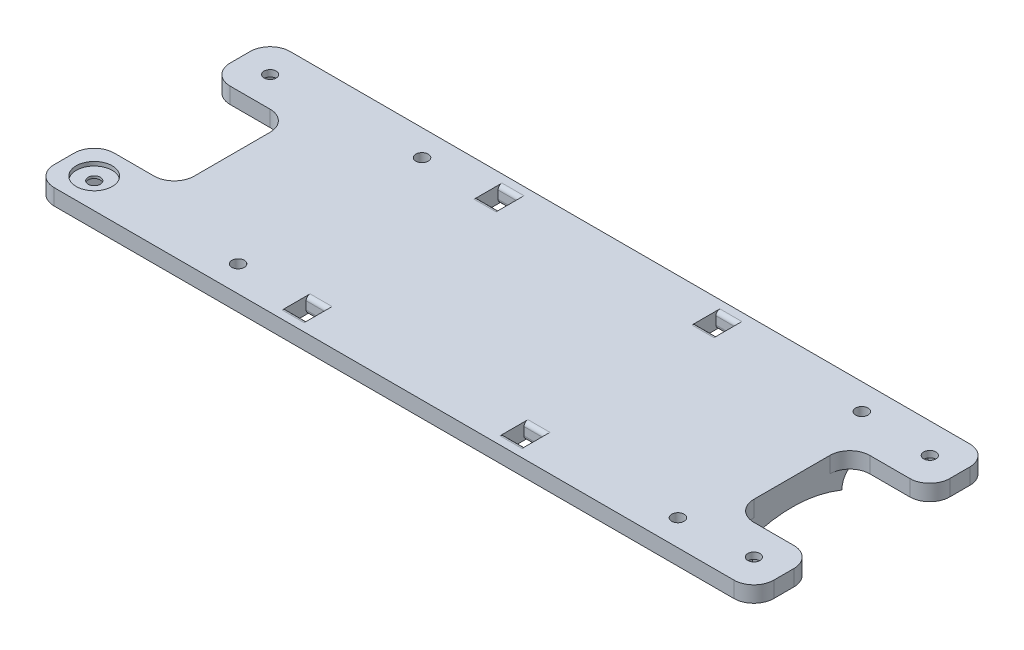
SolidWorks part; units mm, degrees
ref_plane "Front Plane" through (0, 0, 0) normal (0, 0, 1) x (1, 0, 0)
ref_plane "Top Plane" through (0, 0, 0) normal (0, 1, 0) x (1, 0, 0)
ref_plane "Right Plane" through (0, 0, 0) normal (1, 0, 0) x (0, 0, -1)
sketch "Sketch1" plane through (0, 0, 0) normal (0, 1, 0) x (1, 0, 0)
  line L0 (-94.307, 45.1379) -> (-94.307, 16.1379)
  line L1 (-68.307, 1.1379) -> (45.693, 1.1379)
  line L2 (45.693, 16.1379) -> (45.693, 45.1379)
  line L3 (45.693, 60.1379) -> (-68.307, 60.1379)
  line L4 (-68.307, 60.1379) -> (-114.307, 60.1379)
  line L5 (-114.307, 60.1379) -> (-114.307, 45.1379)
  line L6 (-114.307, 45.1379) -> (-94.307, 45.1379)
  line L7 (-68.307, 1.1379) -> (-114.307, 1.1379)
  line L8 (-114.307, 1.1379) -> (-114.307, 16.1379)
  line L9 (-114.307, 16.1379) -> (-94.307, 16.1379)
  line L10 (45.693, 1.1379) -> (65.693, 1.1379)
  line L11 (65.693, 1.1379) -> (65.693, 16.1379)
  line L12 (65.693, 16.1379) -> (45.693, 16.1379)
  line L13 (45.693, 60.1379) -> (65.693, 60.1379)
  line L14 (65.693, 60.1379) -> (65.693, 45.1379)
  line L15 (65.693, 45.1379) -> (45.693, 45.1379)
  dimension "D1" = 59
  dimension "D2" = 140
  dimension "D3" = 20
  dimension "D4" = 15
  dimension "D5" = 15
  dimension "D6" = 20
  dimension "D7" = 15
  dimension "D8" = 15
  dimension "D10" = 20
  dimension "D11" = 20
extrude "Boss-Extrude1" add sketch "Sketch1" along normal blind 4
sketch "Sketch2" plane through (0, 4, 0) normal (0, 1, 0) x (1, 0, 0)
  line L0 (-91.307, 56.1379) -> (-91.307, 5.1379)
  line L1 (-91.307, 5.1379) -> (42.693, 5.1379)
  line L2 (42.693, 5.1379) -> (42.693, 56.1379)
  line L3 (42.693, 56.1379) -> (-91.307, 56.1379)
  line L4 (-94.307, 45.1379) -> (-94.307, 16.1379) construction
  line L5 (-114.307, 1.1379) -> (65.693, 1.1379) construction
  line L6 (65.693, 60.1379) -> (-114.307, 60.1379) construction
  line L7 (45.693, 16.1379) -> (45.693, 45.1379) construction
  circle A0 centre (40.193, 53.6379) radius 1.55
  circle A1 centre (-69.807, 53.6379) radius 1.55
  circle A2 centre (-69.807, 7.6379) radius 1.55
  circle A3 centre (40.193, 7.6379) radius 1.55
  dimension "D8" = 134
  dimension "D1" = 3
  dimension "D2" = 4
  dimension "D3" = 51
  dimension "D4" = 46
  dimension "D5" = 2.5
  dimension "D6" = 110
  dimension "D7" = 2.5
  dimension "D9" = 4
  dimension "D10" = 3
  dimension "D11" = 2.5
extrude "Cut-Extrude3" cut sketch "Sketch2" against normal through all contours A1 | A0 | A3 | A2
sketch "Sketch4" plane through (-31.1286, 4, 0) normal (0, -1, 0) x (-1, 0, 0)
  line L0 (-2.0878, 37.6677) -> (-4.2934, 41.8667)
  line L1 (-4.2934, 22.1365) -> (-2.0878, 26.3345)
  line L2 (-6.4961, 26.3345) -> (-4.2934, 22.1365)
  line L3 (-4.2934, 41.8667) -> (-6.4961, 37.6677)
  line L4 (-7.5369, 37.6677) -> (-9.7405, 41.8667)
  line L5 (-9.7405, 22.1365) -> (-7.5369, 26.3345)
  line L6 (-11.9452, 26.3345) -> (-9.7405, 22.1365)
  line L7 (-9.7405, 41.8667) -> (-11.9452, 37.6677)
  line L8 (-12.985, 37.6677) -> (-15.1887, 41.8667)
  line L9 (-15.1887, 22.1365) -> (-12.985, 26.3345)
  line L10 (-17.3923, 26.3345) -> (-15.1887, 22.1365)
  line L11 (-15.1887, 41.8667) -> (-17.3923, 37.6677)
  line L12 (11.3891, 26.0259) -> (11.3891, 23.4065)
  line L13 (5.0401, 28.613) -> (7.2864, 28.613)
  line L14 (0.9374, 23.4065) -> (0.9374, 26.0259)
  line L15 (11.1698, 23.1873) -> (1.1566, 23.1873)
  line L16 (2.1597, 24.8492) -> (10.1677, 24.8492)
  line L17 (2.1597, 25.7729) -> (2.1597, 24.8492)
  line L18 (7.4015, 26.9283) -> (4.925, 26.9283)
  line L19 (10.1677, 24.8492) -> (10.1677, 25.7729)
  line L20 (3.775, 40.7584) -> (11.1698, 40.7584)
  line L21 (11.1698, 35.353) -> (3.775, 35.353)
  line L22 (11.3891, 36.7956) -> (11.3891, 35.5722)
  line L23 (3.777, 37.0159) -> (11.1698, 37.0159)
  line L24 (11.1698, 39.0955) -> (3.777, 39.0955)
  line L25 (11.3891, 40.5391) -> (11.3891, 39.3148)
  line L26 (10.0685, 32.8546) -> (1.1566, 32.8546)
  line L27 (10.0685, 34.4273) -> (10.0685, 32.8546)
  line L28 (11.1698, 34.647) -> (10.2877, 34.647)
  line L29 (11.3891, 29.505) -> (11.3891, 34.4273)
  line L30 (10.2877, 29.2848) -> (11.1698, 29.2848)
  line L31 (10.0685, 31.0771) -> (10.0685, 29.505)
  line L32 (1.1566, 31.0771) -> (10.0685, 31.0771)
  line L33 (0.9374, 32.6364) -> (0.9374, 31.2964)
  spline S0 degree 3 poles (-2.0878, 26.3345) (-4.2032, 31.7727) (-4.2032, 32.2315) (-2.0878, 37.6677) knots 4 4 4 4 5 5 5 5
  spline S1 degree 3 poles (-6.4961, 37.6677) (-4.3817, 32.2315) (-4.3817, 31.7727) (-6.4961, 26.3345) knots 1 1 1 1 2 2 2 2
  spline S2 degree 3 poles (-7.5369, 26.3345) (-9.6513, 31.7727) (-9.6513, 32.2315) (-7.5369, 37.6677) knots 4 4 4 4 5 5 5 5
  spline S3 degree 3 poles (-11.9452, 37.6677) (-9.8298, 32.2315) (-9.8298, 31.7727) (-11.9452, 26.3345) knots 1 1 1 1 2 2 2 2
  spline S4 degree 3 poles (-12.985, 26.3345) (-15.1003, 31.7727) (-15.1003, 32.2315) (-12.985, 37.6677) knots 4 4 4 4 5 5 5 5
  spline S5 degree 3 poles (-17.3923, 37.6677) (-15.2779, 32.2315) (-15.2779, 31.7727) (-17.3923, 26.3345) knots 1 1 1 1 2 2 2 2
  spline S6 degree 3 poles (10.6707, 28.0401) (11.1579, 27.664) (11.3891, 27.0434) (11.3891, 26.0259) knots 10 10 10 10 11 11 11 11
  spline S7 degree 3 poles (7.2864, 28.613) (8.9324, 28.613) (10.006, 28.5952) (10.6707, 28.0401) knots 9 9 9 9 10 10 10 10
  spline S8 degree 3 poles (1.6557, 28.0401) (2.3205, 28.5952) (3.394, 28.613) (5.0401, 28.613) knots 7 7 7 7 8 8 8 8
  spline S9 degree 3 poles (0.9374, 26.0259) (0.9374, 27.0434) (1.1686, 27.664) (1.6557, 28.0401) knots 6 6 6 6 7 7 7 7
  spline S10 degree 3 poles (0.9959, 23.2448) (0.9612, 23.28) (0.9374, 23.3282) (0.9374, 23.4065) knots 4 4 4 4 5 5 5 5
  spline S11 degree 3 poles (1.1566, 23.1873) (1.0783, 23.1873) (1.0306, 23.2101) (0.9959, 23.2448) knots 3 3 3 3 4 4 4 4
  spline S12 degree 3 poles (11.3315, 23.2448) (11.2958, 23.2101) (11.2492, 23.1873) (11.1698, 23.1873) knots 1 1 1 1 2 2 2 2
  spline S13 degree 3 poles (11.3891, 23.4065) (11.3891, 23.3282) (11.3653, 23.28) (11.3315, 23.2448) knots 0 0 0 0 1 1 1 1
  spline S14 degree 3 poles (2.4515, 26.6128) (2.2252, 26.4243) (2.1597, 26.1807) (2.1597, 25.7729) knots 5 5 5 5 6 6 6 6
  spline S15 degree 3 poles (4.925, 26.9283) (3.5052, 26.9283) (2.8007, 26.9035) (2.4515, 26.6128) knots 4 4 4 4 5 5 5 5
  spline S16 degree 3 poles (9.875, 26.6128) (9.5257, 26.9035) (8.8213, 26.9283) (7.4015, 26.9283) knots 2 2 2 2 3 3 3 3
  spline S17 degree 3 poles (10.1677, 25.7729) (10.1677, 26.1807) (10.1012, 26.4243) (9.875, 26.6128) knots 1 1 1 1 2 2 2 2
  spline S18 degree 3 poles (1.5545, 40.1606) (2.1111, 40.6398) (2.7759, 40.7584) (3.775, 40.7584) knots 20 20 20 20 21 21 21 21
  spline S19 degree 3 poles (0.8054, 38.0607) (0.8054, 39.09) (1.0812, 39.7528) (1.5545, 40.1606) knots 19 19 19 19 20 20 20 20
  spline S20 degree 3 poles (1.5535, 35.927) (1.0644, 36.371) (0.8054, 37.0432) (0.8054, 38.0607) knots 18 18 18 18 19 19 19 19
  spline S21 degree 3 poles (3.775, 35.353) (2.6985, 35.353) (2.0238, 35.4993) (1.5535, 35.927) knots 17 17 17 17 18 18 18 18
  spline S22 degree 3 poles (11.3315, 35.4115) (11.2958, 35.3758) (11.2492, 35.353) (11.1698, 35.353) knots 15 15 15 15 16 16 16 16
  spline S23 degree 3 poles (11.3891, 35.5722) (11.3891, 35.4934) (11.3653, 35.4452) (11.3315, 35.4115) knots 14 14 14 14 15 15 15 15
  spline S24 degree 3 poles (11.3315, 36.9563) (11.3653, 36.9226) (11.3891, 36.8745) (11.3891, 36.7956) knots 12 12 12 12 13 13 13 13
  spline S25 degree 3 poles (11.1698, 37.0159) (11.2492, 37.0159) (11.2958, 36.9916) (11.3315, 36.9563) knots 11 11 11 11 12 12 12 12
  spline S26 degree 3 poles (2.2738, 37.3249) (2.5348, 37.0878) (2.9783, 37.0159) (3.777, 37.0159) knots 9 9 9 9 10 10 10 10
  spline S27 degree 3 poles (1.9941, 38.0393) (1.9941, 37.7327) (2.0794, 37.5016) (2.2738, 37.3249) knots 8 8 8 8 9 9 9 9
  spline S28 degree 3 poles (2.2719, 38.7869) (2.0853, 38.6168) (1.9941, 38.3757) (1.9941, 38.0393) knots 7 7 7 7 8 8 8 8
  spline S29 degree 3 poles (3.777, 39.0955) (3.0061, 39.0955) (2.5477, 39.037) (2.2719, 38.7869) knots 6 6 6 6 7 7 7 7
  spline S30 degree 3 poles (11.3315, 39.154) (11.2958, 39.1188) (11.2492, 39.0955) (11.1698, 39.0955) knots 4 4 4 4 5 5 5 5
  spline S31 degree 3 poles (11.3891, 39.3148) (11.3891, 39.2364) (11.3653, 39.1888) (11.3315, 39.154) knots 3 3 3 3 4 4 4 4
  spline S32 degree 3 poles (11.3315, 40.6999) (11.3653, 40.6656) (11.3891, 40.617) (11.3891, 40.5391) knots 1 1 1 1 2 2 2 2
  spline S33 degree 3 poles (11.1698, 40.7584) (11.2492, 40.7584) (11.2958, 40.7346) (11.3315, 40.6999) knots 0 0 0 0 1 1 1 1
  spline S34 degree 3 poles (10.126, 34.5895) (10.0913, 34.5543) (10.0685, 34.5061) (10.0685, 34.4273) knots 17 17 17 17 18 18 18 18
  spline S35 degree 3 poles (10.2877, 34.647) (10.2094, 34.647) (10.1607, 34.6227) (10.126, 34.5895) knots 16 16 16 16 17 17 17 17
  spline S36 degree 3 poles (11.3315, 34.5895) (11.2958, 34.6227) (11.2492, 34.647) (11.1698, 34.647) knots 14 14 14 14 15 15 15 15
  spline S37 degree 3 poles (11.3891, 34.4273) (11.3891, 34.5061) (11.3653, 34.5543) (11.3315, 34.5895) knots 13 13 13 13 14 14 14 14
  spline S38 degree 3 poles (11.3315, 29.3433) (11.3653, 29.379) (11.3891, 29.4261) (11.3891, 29.505) knots 11 11 11 11 12 12 12 12
  spline S39 degree 3 poles (11.1698, 29.2848) (11.2492, 29.2848) (11.2958, 29.3086) (11.3315, 29.3433) knots 10 10 10 10 11 11 11 11
  spline S40 degree 3 poles (10.126, 29.3433) (10.1607, 29.3086) (10.2094, 29.2848) (10.2877, 29.2848) knots 8 8 8 8 9 9 9 9
  spline S41 degree 3 poles (10.0685, 29.505) (10.0685, 29.4261) (10.0913, 29.379) (10.126, 29.3433) knots 7 7 7 7 8 8 8 8
  spline S42 degree 3 poles (0.9959, 31.1357) (1.0306, 31.1) (1.0783, 31.0771) (1.1566, 31.0771) knots 4 4 4 4 5 5 5 5
  spline S43 degree 3 poles (0.9374, 31.2964) (0.9374, 31.2185) (0.9612, 31.1699) (0.9959, 31.1357) knots 3 3 3 3 4 4 4 4
  spline S44 degree 3 poles (0.9959, 32.7971) (0.9612, 32.7619) (0.9374, 32.7142) (0.9374, 32.6364) knots 1 1 1 1 2 2 2 2
  spline S45 degree 3 poles (1.1566, 32.8546) (1.0783, 32.8546) (1.0306, 32.8318) (0.9959, 32.7971) knots 0 0 0 0 1 1 1 1
extrude "Boss-Extrude2" [suppressed] add sketch "Sketch4" against normal blind 1.6
fillet "Fillet1" radius 5 12 edges at (-114.307, 2, -45.1379) (-114.307, 2, -60.1379) (-114.307, 2, -1.1379) (65.693, 2, -60.1379) (45.693, 2, -45.1379) (65.693, 2, -45.1379) (65.693, 2, -1.1379) (-114.307, 2, -16.1379) (65.693, 2, -16.1379) (45.693, 2, -16.1379) (-94.307, 2, -16.1379) (-94.307, 2, -45.1379)
sketch "Sketch5" plane through (0, 4, 0) normal (0, 1, 0) x (1, 0, 0)
  line L0 (60.693, 60.1379) -> (-109.307, 60.1379) construction
  line L1 (-114.307, 55.1379) -> (-114.307, 50.1379) construction
  line L2 (-99.307, 16.1379) -> (-109.307, 16.1379) construction
  line L3 (-114.307, 11.1379) -> (-114.307, 6.1379) construction
  line L4 (60.693, 16.1379) -> (50.693, 16.1379) construction
  line L5 (65.693, 6.1379) -> (65.693, 11.1379) construction
  line L6 (65.693, 50.1379) -> (65.693, 55.1379) construction
  circle A0 centre (-106.807, 52.6379) radius 1.525
  circle A2 centre (-106.807, 8.6379) radius 1.525
  circle A3 centre (58.193, 8.6379) radius 1.525
  circle A4 centre (58.193, 52.6379) radius 1.525
  circle A5 centre (-106.807, 8.6379) radius 4.5
  dimension "D1" = 3.05
  dimension "D7" = 3.05
  dimension "D10" = 3.05
  dimension "D13" = 3.05
  dimension "D14" = 9
  dimension "D2" = 7.5
  dimension "D3" = 7.5
  dimension "D5" = 7.5
  dimension "D6" = 7.5
  dimension "D8" = 7.5
  dimension "D9" = 7.5
  dimension "D11" = 7.5
  dimension "D12" = 7.5
extrude "Cut-Extrude4" cut sketch "Sketch5" against normal blind 10 contours A0 | A2 | A3 | A4
extrude "Cut-Extrude5" cut sketch "Sketch5<3>" against normal blind 1 contours A5
sketch "Sketch5<3>" plane through (0, 4, 0) normal (0, 1, 0) x (1, 0, 0) same geometry as "Sketch5"
sketch "Sketch6" plane through (0, 0, 0) normal (0, -1, 0) x (1, 0, 0)
  line L1 (-104.663, -11.0193) -> (-103.6727, -7.9718)
  line L2 (-103.6727, -7.9718) -> (-105.8167, -5.5905)
  line L3 (-105.8167, -5.5905) -> (-108.951, -6.2566)
  line L4 (-108.951, -6.2566) -> (-109.9413, -9.304)
  line L5 (-109.9413, -9.304) -> (-107.7973, -11.6854)
  line L6 (-107.7973, -11.6854) -> (-104.663, -11.0193)
  line L7 (58.7701, -11.7898) -> (61.2112, -9.7141)
  line L8 (61.2112, -9.7141) -> (60.6341, -6.5622)
  line L9 (60.6341, -6.5622) -> (57.6159, -5.486)
  line L10 (57.6159, -5.486) -> (55.1748, -7.5618)
  line L11 (55.1748, -7.5618) -> (55.7519, -10.7137)
  line L12 (55.7519, -10.7137) -> (58.7701, -11.7898)
  line L13 (60.6824, -50.6205) -> (57.6905, -49.4733)
  line L14 (57.6905, -49.4733) -> (55.2011, -51.4908)
  line L15 (55.2011, -51.4908) -> (55.7035, -54.6554)
  line L16 (55.7035, -54.6554) -> (58.6955, -55.8026)
  line L17 (58.6955, -55.8026) -> (61.1849, -53.7851)
  line L18 (61.1849, -53.7851) -> (60.6824, -50.6205)
  line L19 (-103.607, -52.4732) -> (-105.3497, -49.7842)
  line L20 (-105.3497, -49.7842) -> (-108.5497, -49.949)
  line L21 (-108.5497, -49.949) -> (-110.0071, -52.8027)
  line L22 (-110.0071, -52.8027) -> (-108.2644, -55.4916)
  line L23 (-108.2644, -55.4916) -> (-105.0643, -55.3269)
  line L24 (-105.0643, -55.3269) -> (-103.607, -52.4732)
  circle A0 centre (-106.807, -8.6379) radius 2.775 construction
  circle A1 centre (58.193, -8.6379) radius 2.775 construction
  circle A2 centre (58.193, -52.6379) radius 2.775 construction
  circle A3 centre (-106.807, -52.6379) radius 2.775 construction
  circle A4 centre (58.193, -52.6379) radius 1.525 construction
  point P40 (-104.3356, -53.9)
  dimension "D1" = 5.55
  dimension "D2" = 5.55
  dimension "D3" = 5.55
  dimension "D4" = 5.55
extrude "Cut-Extrude6" cut sketch "Sketch6" against normal blind 2.4
sketch "Sketch8" plane through (0, 0, 0) normal (0, -1, 0) x (1, 0, 0)
  line L0 (45.693, -18.1379) -> (-94.307, -18.1379)
  line L3 (-94.307, -18.1379) -> (-94.307, -43.1379)
  line L4 (-94.307, -43.1379) -> (45.693, -43.1379)
  line L5 (45.693, -43.1379) -> (45.693, -18.1379)
  line L6 (-94.307, -40.1379) -> (-94.307, -21.1379) construction
  line L7 (45.693, -21.1379) -> (45.693, -40.1379) construction
  line L8 (-94.307, -30.6379) -> (45.693, -30.6379) construction
  dimension "D1" = 25
  dimension "D2" = 12.5
extrude "Boss-Extrude4" add sketch "Sketch8" along normal blind 5
sketch "Sketch9" plane through (-94.307, 0, -95.4449) normal (1, 0, 0) x (0, 0, -1)
  line L0 (-52.307, -5) -> (-77.307, -5)
  line L1 (-77.307, -5) -> (-52.307, -5) construction
  spline S0 degree 2 poles (-52.307, -5) (-64.7313, 0.0282) (-77.307, -5) knots 0 0 0 1 1 1
  point P8 (0, 0)
  point P12 (0, 0)
  point P14 (0, 0)
  dimension "D1" = 2.5
extrude "Cut-Extrude7" cut sketch "Sketch9" along normal through all
sketch "Sketch12" plane through (0, 0, 0) normal (0, -1, 0) x (1, 0, 0)
  line L0 (-54.307, -9.1379) -> (-48.807, -9.1379)
  line L1 (-48.807, -9.1379) -> (-48.807, -4.1379)
  line L2 (-48.807, -4.1379) -> (-54.307, -4.1379)
  line L3 (-54.307, -4.1379) -> (-54.307, -9.1379)
  line L4 (-109.307, -1.1379) -> (60.693, -1.1379) construction
  line L6 (-94.307, -18.1379) -> (-94.307, -43.1379) construction
  line L7 (0.193, -4.1379) -> (0.193, -9.1379)
  line L8 (0.193, -9.1379) -> (5.693, -9.1379)
  line L9 (5.693, -9.1379) -> (5.693, -4.1379)
  line L10 (5.693, -4.1379) -> (0.193, -4.1379)
  line L11 (45.693, -43.1379) -> (45.693, -18.1379) construction
  line L12 (-94.307, -30.6379) -> (45.693, -30.6379) construction
  line L13 (5.693, -57.1379) -> (0.193, -57.1379)
  line L14 (5.693, -52.1379) -> (5.693, -57.1379)
  line L15 (0.193, -52.1379) -> (5.693, -52.1379)
  line L16 (0.193, -57.1379) -> (0.193, -52.1379)
  line L17 (-54.307, -57.1379) -> (-54.307, -52.1379)
  line L18 (-48.807, -57.1379) -> (-54.307, -57.1379)
  line L19 (-48.807, -52.1379) -> (-48.807, -57.1379)
  line L20 (-54.307, -52.1379) -> (-48.807, -52.1379)
  dimension "D1" = 5
  dimension "D2" = 5.5
  dimension "D3" = 3
  dimension "D4" = 40
  dimension "D5" = 5.5
  dimension "D6" = 5
  dimension "D7" = 3
  dimension "D8" = 40
fillet "Fillet5" radius 5 2 edges at (-24.307, 0, -43.1379) (-24.307, 0, -18.1379)
extrude "Cut-Extrude8" cut sketch "Sketch12" against normal blind 10
fillet "Fillet6" radius 1 16 edges at (-51.557, 0, -57.1379) (-51.557, 4, -57.1379) (-51.557, 0, -52.1379) (-51.557, 4, -52.1379) (2.943, 0, -52.1379) (2.943, 4, -52.1379) (2.943, 0, -57.1379) (2.943, 4, -57.1379) (2.943, 0, -4.1379) (2.943, 4, -4.1379) (2.943, 0, -9.1379) (2.943, 4, -9.1379) (-51.557, 4, -9.1379) (-51.557, 0, -9.1379) (-51.557, 0, -4.1379) (-51.557, 4, -4.1379)
equation "\"1.6.00mm\"=2"
